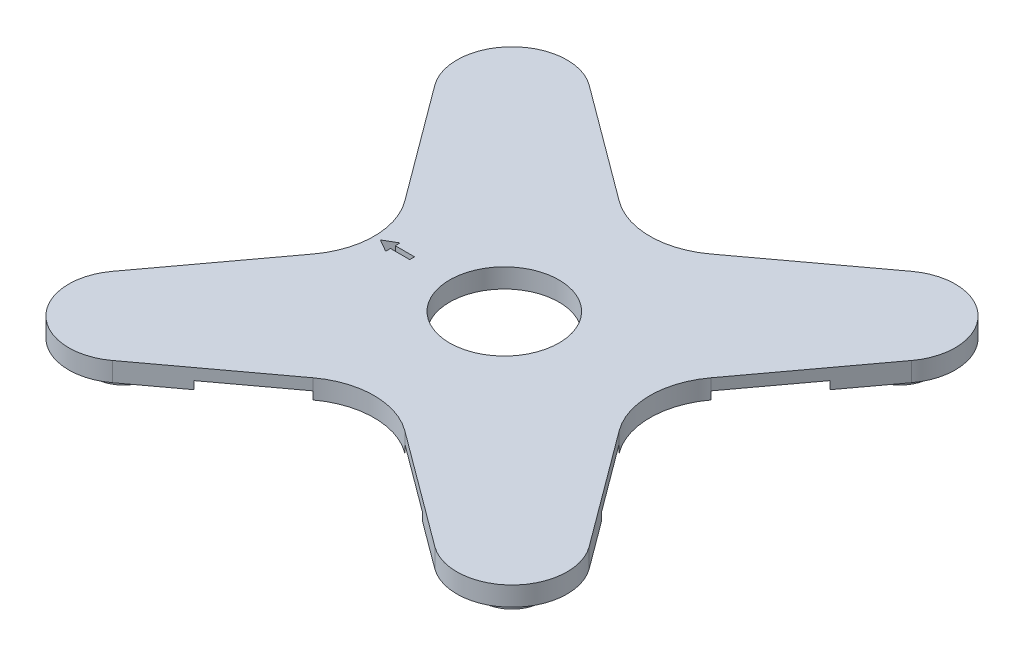
SolidWorks part; units mm, degrees
ref_plane "Front Plane" through (0, 0, 0) normal (0, 0, 1) x (1, 0, 0)
ref_plane "Top Plane" through (0, 0, 0) normal (0, 1, 0) x (1, 0, 0)
ref_plane "Right Plane" through (0, 0, 0) normal (1, 0, 0) x (0, 0, -1)
sketch "Sketch1" plane through (0, 0, 0) normal (0, 1, 0) x (1, 0, 0)
  line L0 (-25.2318, 7.5541) -> (-39.3151, 26.5872)
  line L1 (-26.5872, 39.3151) -> (-7.5541, 25.2318)
  line L2 (7.5541, 25.2318) -> (26.5872, 39.3151)
  line L3 (39.3151, 26.5872) -> (25.2318, 7.5541)
  line L4 (25.2318, -7.5541) -> (39.3151, -26.5872)
  line L5 (26.5872, -39.3151) -> (7.5541, -25.2318)
  line L6 (-7.5541, -25.2318) -> (-26.5872, -39.3151)
  line L7 (-39.3151, -26.5872) -> (-25.2318, -7.5541)
  line L8 (-32, 32) -> (32, -32) construction
  line L9 (-32, -32) -> (32, 32) construction
  line L10 (-32, -32) -> (32, -32) construction
  line L11 (-32, 32) -> (-32, -32) construction
  line L12 (-32, 32) -> (32, 32) construction
  line L13 (32, 32) -> (32, -32) construction
  line L14 (-25.2318, -7.5541) -> (-7.5541, -25.2318) construction
  line L15 (-25.2318, 7.5541) -> (-7.5541, 25.2318) construction
  line L16 (7.5541, 25.2318) -> (25.2318, 7.5541) construction
  line L17 (25.2318, -7.5541) -> (7.5541, -25.2318) construction
  line L25 (-19.6422, 0.3969) -> (-16.4672, 0.3969)
  line L26 (-19.6422, 0.3969) -> (-19.6422, -0.3969)
  line L27 (-19.6422, -0.3969) -> (-16.4672, -0.3969)
  line L28 (-16.4672, 0.3969) -> (-16.4672, -0.3969)
  line L29 (-19.6422, -1.1906) -> (-21.7044, 0)
  line L30 (-21.7044, 0) -> (-19.6422, 1.1906)
  line L31 (-19.6422, 1.1906) -> (-19.6422, -1.1906)
  circle A0 centre (0, 0) radius 7.9375 construction
  circle A1 centre (0, 0) radius 9.525 construction
  circle A2 centre (-1.27, 0) radius 9.017
  arc A3 (-39.3151, 26.5872) -> (-26.5872, 39.3151) centre (-32, 32) cw
  arc A4 (-7.5541, 25.2318) -> (7.5541, 25.2318) centre (0, 19.6422) cw
  arc A5 (26.5872, 39.3151) -> (39.3151, 26.5872) centre (32, 32) cw
  arc A6 (25.2318, 7.5541) -> (25.2318, -7.5541) centre (19.6422, 0) cw
  arc A7 (39.3151, -26.5872) -> (26.5872, -39.3151) centre (32, -32) cw
  arc A8 (7.5541, -25.2318) -> (-7.5541, -25.2318) centre (0, -19.6422) cw
  arc A9 (-26.5872, -39.3151) -> (-39.3151, -26.5872) centre (-32, -32) cw
  arc A10 (-25.2318, -7.5541) -> (-25.2318, 7.5541) centre (-19.6422, 0) cw
  circle A11 centre (-32, 32) radius 5
  circle A12 centre (32, 32) radius 5
  circle A13 centre (-32, -32) radius 5
  circle A14 centre (32, -32) radius 5
  arc A15 (-25.2318, 7.5541) -> (-25.2318, -7.5541) centre (-35.4409, 0) cw
  arc A16 (-7.5541, -25.2318) -> (7.5541, -25.2318) centre (0, -35.4409) cw
  arc A17 (-7.5541, 25.2318) -> (7.5541, 25.2318) centre (0, 35.4409) ccw
  arc A18 (25.2318, -7.5541) -> (25.2318, 7.5541) centre (35.4409, 0) cw
  point P34 (-16.3929, -16.3929)
  point P35 (16.3929, -16.3929)
  point P36 (-16.3929, 16.3929)
  point P37 (16.3929, 16.3929)
  point P38 (0, 0)
  point P47 (-19.6422, 0)
  point P51 (-19.6422, 0)
  dimension "D1" = 15.875
  dimension "D2" = 19.05
  dimension "D3" = 18.034
  dimension "D6" = 10
  dimension "D9" = 12.7
  dimension "D4" = 1.27
  dimension "D5" = 64
  dimension "D7" = 18
  dimension "D8" = 25
  dimension "D10" = 0.7937
  dimension "D11" = 0.7937
  dimension "D12" = 3.175
  dimension "D13" = 30
extrude "Boss-Extrude1" add sketch "Sketch1" along normal blind 3.175 contours L4 A18 L3 A5 L2 A17 L1 A3 L0 A15 L7 A9 L6 A16 L5 A7 A14 A13 A12 A11 A2 region at (-31.339, 0, -17.7621)
extrude "Boss-Extrude2" add sketch "Sketch1<3>" against normal blind 6.35 from surface contours A11 | A14 | A12 | A13 region at (-32, 0, -32) region at (32, 0, -32) region at (-32, 0, 32) region at (32, 0, 32) starting at face at (32, 3.175, 37)
sketch "Sketch1<3>" plane through (0, 0, 0) normal (0, 1, 0) x (1, 0, 0) same geometry as "Sketch1"
sketch "Sketch2" plane through (0, 0, 0) normal (0, -1, 0) x (1, 0, 0)
  line L0 (-6.4623, -24.4239) -> (-24.4239, -6.4623)
  line L1 (-26.5872, -39.3151) -> (-7.5541, -25.2318) construction
  line L2 (-25.2318, -7.5541) -> (-39.3151, -26.5872) construction
  line L3 (-24.4239, -6.4623) -> (-33.5895, -18.8493)
  line L4 (-33.5895, -18.8493) -> (-18.8493, -33.5895)
  line L5 (-18.8493, -33.5895) -> (-6.4623, -24.4239)
  line L6 (-15.4431, -15.4431) -> (-32, -32) construction
  line L7 (55, 0) -> (-55, 0) construction
  line L8 (-33.5895, 18.8493) -> (-18.8493, 33.5895)
  line L9 (-24.4239, 6.4623) -> (-33.5895, 18.8493)
  line L10 (-6.4623, 24.4239) -> (-24.4239, 6.4623)
  line L11 (-18.8493, 33.5895) -> (-6.4623, 24.4239)
  line L12 (0, -55) -> (0, 55) construction
  line L13 (24.4239, 6.4623) -> (33.5895, 18.8493)
  line L14 (6.4623, 24.4239) -> (24.4239, 6.4623)
  line L15 (18.8493, 33.5895) -> (6.4623, 24.4239)
  line L16 (33.5895, 18.8493) -> (18.8493, 33.5895)
  line L17 (33.5895, -18.8493) -> (18.8493, -33.5895)
  line L18 (24.4239, -6.4623) -> (33.5895, -18.8493)
  line L19 (6.4623, -24.4239) -> (24.4239, -6.4623)
  line L20 (18.8493, -33.5895) -> (6.4623, -24.4239)
  circle A0 centre (-32, -32) radius 5 construction
  point P12 (-28.4645, -28.4645)
  dimension "D1" = 15.24
  dimension "D2" = 3.175
extrude "Cut-Extrude1" cut sketch "Sketch2" against normal blind 1.3
